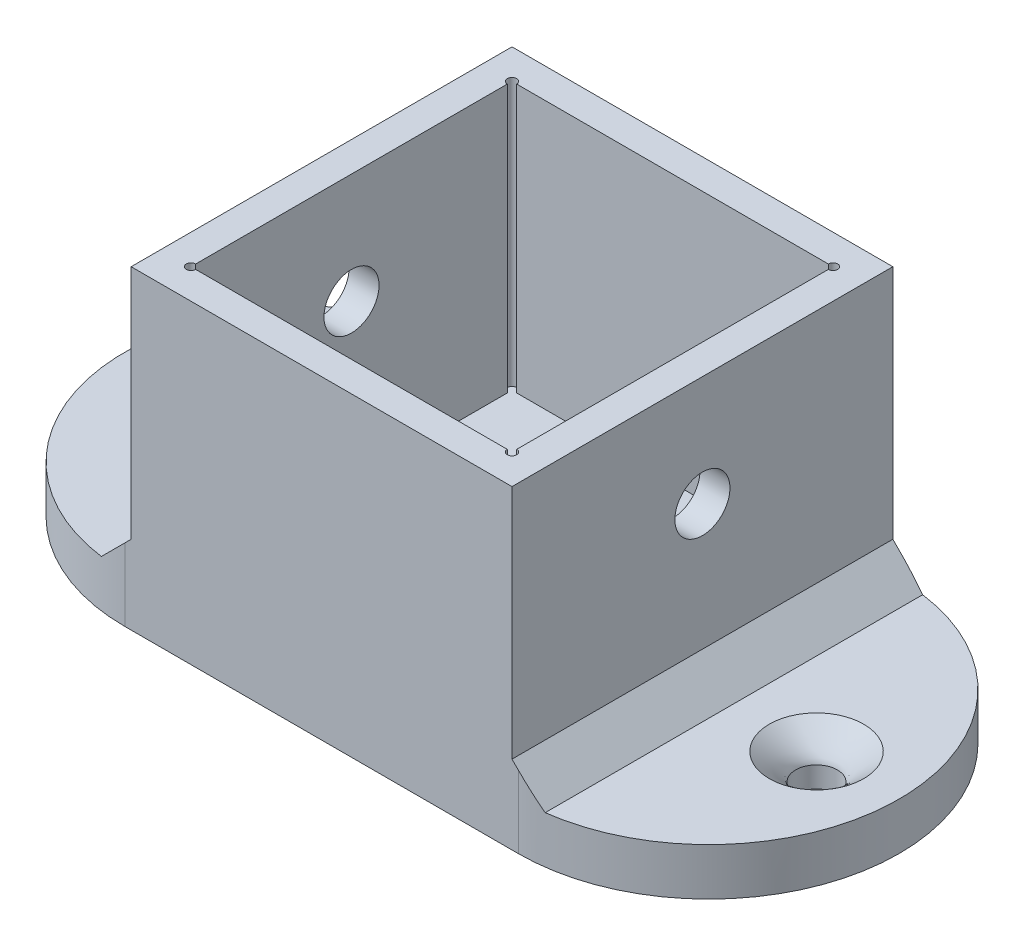
SolidWorks part; units mm, degrees
ref_plane "Front Plane" through (0, 0, 0) normal (0, 0, 1) x (1, 0, 0)
ref_plane "Top Plane" through (0, 0, 0) normal (0, 1, 0) x (1, 0, 0)
ref_plane "Right Plane" through (0, 0, 0) normal (1, 0, 0) x (0, 0, -1)
sketch "Sketch1" plane through (0, 0, 0) normal (0, 1, 0) x (1, 0, 0)
  line L0 (-15.875, 0) -> (15.875, 0) construction
  line L1 (-15.875, 15.367) -> (15.875, 15.367)
  line L2 (-15.875, -15.367) -> (15.875, -15.367)
  line L3 (0, 15.367) -> (0, -15.367) construction
  arc A0 (-15.875, 15.367) -> (-15.875, -15.367) centre (-15.875, 0) ccw
  arc A1 (15.875, -15.367) -> (15.875, 15.367) centre (15.875, 0) ccw
  point P3 (0, 0)
  dimension "D1" = 30.734
  dimension "D2" = 31.75
extrude "Boss-Extrude1" add sketch "Sketch1" along normal blind 3.81
sketch "Sketch2" plane through (0, 3.81, 0) normal (0, 1, 0) x (1, 0, 0)
  line L0 (15.875, 15.367) -> (-15.875, 15.367) construction
  line L1 (-12.954, -12.954) -> (12.954, -12.954)
  line L2 (-12.954, -12.954) -> (-12.954, 12.954)
  line L3 (-12.954, 12.954) -> (12.954, 12.954)
  line L4 (12.954, -12.954) -> (12.954, 12.954)
  line L5 (-12.954, -12.954) -> (12.954, 12.954) construction
  line L6 (-12.954, 12.954) -> (12.954, -12.954) construction
  line L7 (-15.367, -15.367) -> (15.367, -15.367)
  line L8 (-15.367, -15.367) -> (-15.367, 15.367)
  line L9 (-15.367, 15.367) -> (15.367, 15.367)
  line L10 (15.367, -15.367) -> (15.367, 15.367)
  line L11 (-15.367, -15.367) -> (15.367, 15.367) construction
  line L12 (-15.367, 15.367) -> (15.367, -15.367) construction
  point P0 (0, 0)
  point P6 (0, 0)
  dimension "D1" = 2.413
extrude "Boss-Extrude2" add sketch "Sketch2" along normal blind 21.59
chamfer "Chamfer1" distance 2.54 angle 45 2 edges at (15.367, 3.81, 0) (-15.367, 3.81, 0)
sketch "Sketch3" plane through (0, 3.81, 0) normal (0, 1, 0) x (1, 0, 0)
  line L0 (-17.907, 0) -> (-31.242, 0) construction
  line L1 (-17.907, -15.2321) -> (-17.907, 15.2321) construction
  line L2 (0, 15.367) -> (0, -15.367) construction
  line L3 (15.367, 15.367) -> (-15.367, 15.367) construction
  line L4 (-15.367, -15.367) -> (15.367, -15.367) construction
  arc A0 (-17.907, 15.2321) -> (-17.907, -15.2321) centre (-15.875, 0) ccw construction
  circle A1 centre (-24.5745, 0) radius 1.6827
  circle A2 centre (24.5745, 0) radius 1.6827
  dimension "D1" = 3.3655
extrude "Cut-Extrude1" cut sketch "Sketch3" against normal up to surface (3.81 mm away) up to face at (0, 0, 0)
sketch "Sketch4" plane through (0, 3.81, 0) normal (0, 1, 0) x (1, 0, 0)
  circle A0 centre (-24.5745, 0) radius 3.81
  dimension "D1" = 7.62
ref_plane "Plane1" through (0, 1.27, 0) normal (0, 1, 0) x (1, 0, 0)
sketch "Sketch5" plane through (0, 1.27, 0) normal (0, 1, 0) x (1, 0, 0)
  circle A0 centre (-24.5745, 0) radius 1.6827
loft "Cut-Loft1" cut profiles "Sketch5", "Sketch4" connector at (-26.146, 1.27, -0.6017) connector at (-24.2112, 3.81, -3.7926)
mirror "Mirror1" about plane through (0, 0, 0) normal (1, 0, 0) of "Cut-Loft1"
sketch "Sketch6" plane through (12.954, 0, 0) normal (-1, 0, 0) x (0, 0, 1)
  line L0 (12.954, 3.81) -> (-12.954, 3.81) construction
  circle A0 centre (0, 16.51) radius 2.2225
  dimension "D1" = 12.7
  dimension "D2" = 4.445
extrude "Cut-Extrude2" cut sketch "Sketch6" against normal through all both and the other way through all
sketch "Sketch7" plane through (0, 0, 0) normal (0, -1, 0) x (-1, 0, 0)
  line L0 (0, 15.367) -> (0, -15.367) construction
  line L1 (-15.875, 15.367) -> (15.875, 15.367) construction
  line L2 (15.875, -15.367) -> (-15.875, -15.367) construction
sketch "Sketch8" plane through (0, 25.4, 0) normal (0, 1, 0) x (1, 0, 0)
  circle A0 centre (-12.954, 12.954) radius 0.381
  circle A1 centre (12.954, 12.954) radius 0.381
  circle A2 centre (12.954, -12.954) radius 0.381
  circle A3 centre (-12.954, -12.954) radius 0.381
  dimension "D1" = 0.762
extrude "Cut-Extrude3" cut sketch "Sketch8" against normal up to surface (21.59 mm away) up to face at (0, 3.81, 0)
